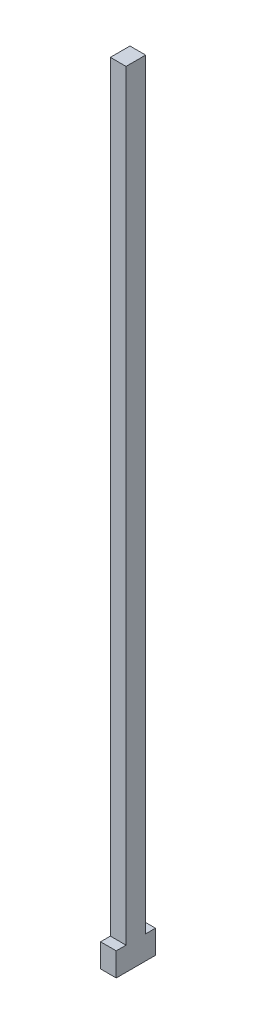
SolidWorks part; units mm, degrees
ref_plane "Front Plane" through (0, 0, 0) normal (0, 0, 1) x (1, 0, 0)
ref_plane "Top Plane" through (0, 0, 0) normal (0, 1, 0) x (1, 0, 0)
ref_plane "Right Plane" through (0, 0, 0) normal (1, 0, 0) x (0, 0, -1)
sketch "Sketch1" plane through (0, 0, 0) normal (0, 1, 0) x (1, 0, 0)
  line L0 (-2, -2.5) -> (-2, -5.0011)
  line L5 (-2, -5.0011) -> (2, -5.0011)
  line L6 (2, -5.0011) -> (2, -2.5)
  line L7 (-2, 2.5) -> (2, 2.5)
  line L8 (-2, 2.5) -> (-2, -2.5)
  line L9 (-2, -2.5) -> (2, -2.5)
  line L10 (2, 2.5) -> (2, -2.5)
  line L11 (-2, 2.5) -> (2, -2.5) construction
  line L12 (-2, -2.5) -> (2, 2.5) construction
  line L13 (-2, 2.5) -> (-2, 5)
  line L14 (-2, 5) -> (2, 5)
  line L15 (2, 5) -> (2, 2.5)
  point P0 (0, 0)
  point P6 (0, 0)
  dimension "D1" = 4
  dimension "D2" = 5
  dimension "D3" = 2.5
  dimension "D4" = 2
  dimension "D5" = 2.5011
  dimension "D6" = 2.5
extrude "Boss-Extrude1" add sketch "Sketch1" along normal blind 6 contours L9 L0 L5 L6 | L15 L14 L13 L7 region at (0, 0, 3.7505) region at (0, 0, -3.75)
extrude "Boss-Extrude2" add sketch "Sketch1<3>" along normal blind 200 contours L10 L7 L8 L9 region at (0, 0, 0)
sketch "Sketch1<3>" plane through (0, 0, 0) normal (0, 1, 0) x (1, 0, 0) same geometry as "Sketch1"
